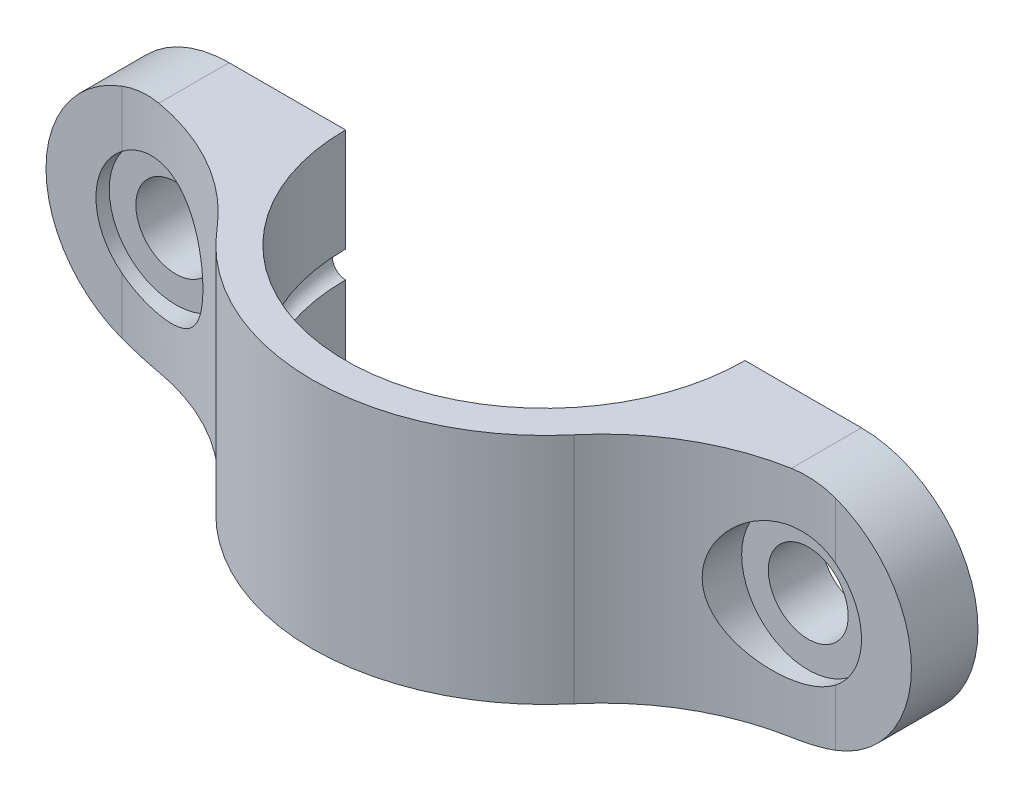
SolidWorks part; units mm, degrees
ref_plane "Front Plane" through (0, 0, 0) normal (0, 0, 1) x (1, 0, 0)
ref_plane "Top Plane" through (0, 0, 0) normal (0, 1, 0) x (1, 0, 0)
ref_plane "Right Plane" through (0, 0, 0) normal (1, 0, 0) x (0, 0, -1)
sketch "Sketch1" plane through (0, 0, 0) normal (0, 1, 0) x (1, 0, 0)
  line L0 (-30, 0) -> (30, 0) construction
  line L1 (30, 0) -> (65, 0)
  line L2 (0, 0) -> (0, -30) construction
  line L3 (-30, 0) -> (-65, 0)
  line L4 (-53.619, -10) -> (-65, -10)
  line L5 (53.619, -10) -> (65, -10)
  line L6 (-30, -10) -> (-65, -10) construction
  line L7 (30, -10) -> (65, -10) construction
  line L8 (-65, 0) -> (-65, -10)
  line L9 (65, 0) -> (65, -10)
  arc A0 (-30, 0) -> (30, 0) centre (0, 0) ccw
  arc A1 (-26.8095, -22.5) -> (26.8095, -22.5) centre (0, 0) ccw
  arc A2 (-35, 0) -> (35, 0) centre (0, 0) ccw construction
  arc A3 (53.619, -10) -> (26.8095, -22.5) centre (53.619, -45) ccw
  arc A4 (-26.8095, -22.5) -> (-53.619, -10) centre (-53.619, -45) ccw
  point P4 (0, 0)
  dimension "D4" = 30
  dimension "D6" = 35
  dimension "D5" = 35
  dimension "D1" = 5
  dimension "D2" = 10
  dimension "D3" = 10
extrude "Boss-Extrude1" add sketch "Sketch1" along normal mid plane 35
sketch "Sketch2" plane through (0, 0, 0) normal (0, 0, -1) x (-1, 0, 0)
  line L1 (-30, 17.5) -> (-30, -17.5) construction
  line L2 (30, 17.5) -> (30, -17.5) construction
  line L3 (30, 17.5) -> (65, 17.5) construction
  line L5 (-65, 17.5) -> (-30, 17.5) construction
  circle A4 centre (47.5, 0) radius 6
  circle A5 centre (-47.5, 0) radius 6
  dimension "D1" = 17.5
  dimension "D2" = 17.5
  dimension "D3" = 12
  dimension "D4" = 12
  dimension "D5" = 17.5
  dimension "D6" = 17.5
extrude "Cut-Extrude1" cut sketch "Sketch2" against normal through all
sketch "Sketch3" plane through (0, 0, 0) normal (0, 0, -1) x (-1, 0, 0)
  line L0 (30, 17.5) -> (30, -17.5) construction
  line L1 (0, 0) -> (0, -24.3708) construction
  circle A0 centre (30, 0) radius 2
  dimension "D1" = 4
revolve "Cut-Revolve1" cut sketch "Sketch3" angle 360 about L1
fillet "Fillet1" 2 edges at (65, 17.5, 5) (65, -17.5, 5) type full round first side face at (0, 17.5, 12.1557) second side face at (0, -17.5, 12.1557) middle face at (65, 0, 5)
fillet "Fillet2" 2 edges at (-65, 17.5, 5) (-65, -17.5, 5) type full round first side face at (-9.8096, 17.5, 12.583) second side face at (-9.8096, -17.5, 12.583) middle face at (-65, 0, 5)
sketch "Sketch4" plane through (0, 0, 0) normal (0, 0, -1) x (-1, 0, 0)
  circle A0 centre (47.5, 0) radius 10
  circle A2 centre (-47.5, 0) radius 10
  dimension "D1" = 20
  dimension "D2" = 20
extrude "Cut-Extrude2" cut sketch "Sketch4" against normal blind 35 from offset 8 offset against normal yes
